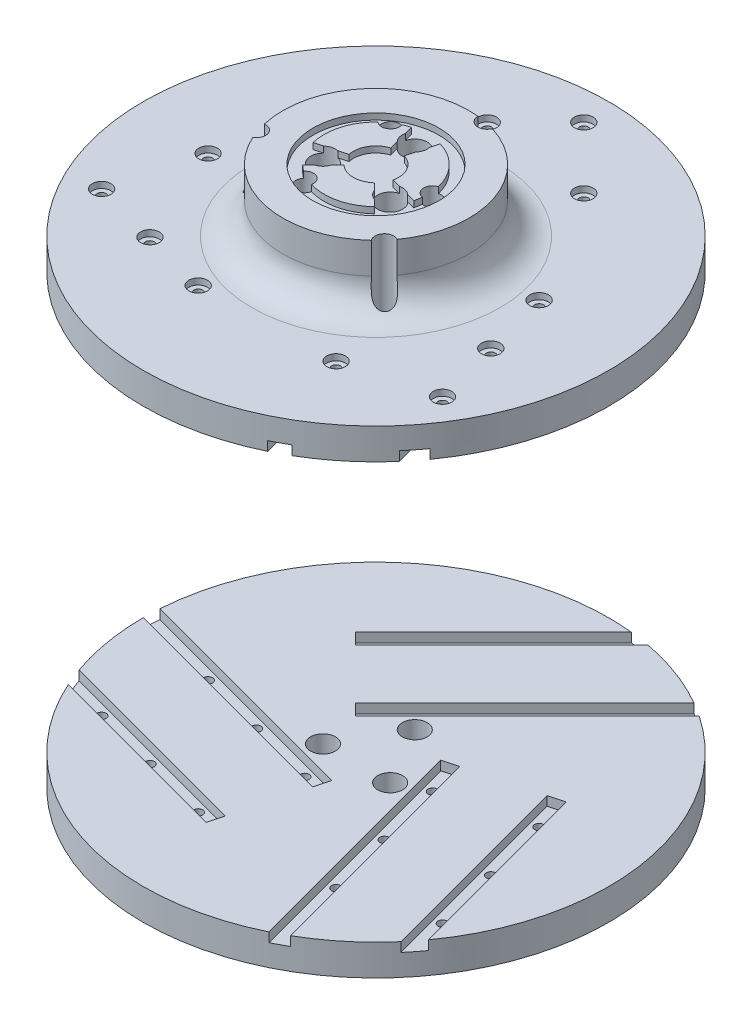
SolidWorks part; units mm, degrees
note: '?' marks a value the reader was unsure of. The reader was unsure of these and kept them because the rebuilt part matched: shared geometry of "草图7<2>", "草图9<2>", "草图14<2>".
ref_plane "前视基准面" through (0, 0, 0) normal (0, 0, 1) x (1, 0, 0)
ref_plane "上视基准面" through (0, 0, 0) normal (0, 1, 0) x (1, 0, 0)
ref_plane "右视基准面" through (0, 0, 0) normal (1, 0, 0) x (0, 0, -1)
sketch "草图1" plane through (0, 0, 0) normal (0, 1, 0) x (1, 0, 0)
  circle A0 centre (0, 0) radius 75
  dimension "D1" = 150
extrude "凸台-拉伸1" add sketch "草图1" along normal blind 10
ref_plane "基准面1" through (0, 144, 0) normal (0, 1, 0) x (1, 0, 0)
sketch "草图2" plane through (0, 144, 0) normal (0, 1, 0) x (1, 0, 0)
  circle A0 centre (0, 0) radius 75
extrude "凸台-拉伸2" add sketch "草图2" along normal blind 10 separate body
sketch "草图3" plane through (0, 154, 0) normal (0, 1, 0) x (1, 0, 0)
  circle A0 centre (0, 0) radius 30
  dimension "D1" = 60
extrude "凸台-拉伸3" add sketch "草图3" along normal blind 20
sketch "草图4" plane through (0, 174, 0) normal (0, 1, 0) x (1, 0, 0)
  line L0 (0, 0) -> (0, 12.5) construction
  line L1 (0, 0) -> (-10.8253, -6.25) construction
  line L2 (0, 0) -> (10.8253, -6.25) construction
  circle A0 centre (0, 0) radius 12.5 construction
  circle A1 centre (0, 12.5) radius 4
  circle A2 centre (-10.8253, -6.25) radius 4
  circle A3 centre (10.8253, -6.25) radius 4
  dimension "D1" = 120
  dimension "D3" = 8
  dimension "D4" = 8
  dimension "D5" = 8
  dimension "D2" = 120
extrude "切除-拉伸1" cut sketch "草图4" against normal through all both and the other way through all
fillet "圆角1" radius 10 1 edges at (0, 154, 30) type face fillet first side face at (0, 174, 30) second side face at (0, 154, 30)
ref_axis "基准轴1" through (-10.8253, 144, 6.25) along (0, 1, 0)?
ref_axis "基准轴2" through (0, 144, -12.5) along (0, 1, 0)?
ref_axis "基准轴3" through (10.8253, 144, 6.25) along (0, 1, 0)?
sketch "草图7" plane through (0, 10, 0) normal (0, 1, 0) x (1, 0, 0)
  line L0 (0, 0) -> (0, 12.5) construction
  line L1 (0, 0) -> (-10.8253, -6.25) construction
  line L2 (0, 0) -> (10.8253, -6.25) construction
  line L3 (0, 12.5) -> (-3.8891, 16.3891) construction
  line L4 (-3.8891, 16.3891) -> (-13.435, 6.8431)
  line L13 (-13.435, 6.8431) -> (-16.9706, 10.3787)
  line L14 (-16.9706, 10.3787) -> (39.598, 66.9472)
  line L15 (39.598, 66.9472) -> (43.1335, 63.4117)
  line L16 (43.1335, 63.4117) -> (-3.8891, 16.3891)
  line L17 (-33.234, 26.6421) -> (16.2635, 76.1396)
  line L18 (16.2635, 76.1396) -> (12.7279, 79.6751)
  line L19 (12.7279, 79.6751) -> (-36.7696, 30.1777)
  line L20 (-36.7696, 30.1777) -> (-33.234, 26.6421)
  line L21 (12.6439, 8.2135) -> (17.4735, 9.5076)
  line L22 (16.1379, -4.8265) -> (12.6439, 8.2135)
  line L23 (17.4735, 9.5076) -> (38.179, -67.7665)
  line L24 (33.3494, -69.0606) -> (16.1379, -4.8265)
  line L25 (38.179, -67.7665) -> (33.3494, -69.0606)
  line L26 (62.6367, -50.8603) -> (44.5194, 16.7545)
  line L27 (39.6898, 15.4604) -> (57.8071, -52.1544)
  line L28 (57.8071, -52.1544) -> (62.6367, -50.8603)
  line L29 (44.5194, 16.7545) -> (39.6898, 15.4604)
  line L30 (0.7912, -15.0566) -> (-0.5029, -19.8863)
  line L31 (-12.2488, -11.5626) -> (0.7912, -15.0566)
  line L32 (-0.5029, -19.8863) -> (-77.777, 0.8192)
  line L33 (-76.4829, 5.6489) -> (-12.2488, -11.5626)
  line L34 (-77.777, 0.8192) -> (-76.4829, 5.6489)
  line L35 (-75.3647, -28.8149) -> (-7.7499, -46.9322)
  line L36 (-6.4558, -42.1026) -> (-74.0706, -23.9852)
  line L37 (-74.0706, -23.9852) -> (-75.3647, -28.8149)
  line L38 (-7.7499, -46.9322) -> (-6.4558, -42.1026)
  line L39 (-15.2028, 8.6109) -> (41.3657, 65.1795) construction
  line L40 (0, 0) -> (-9.5459, 14.2678) construction
  circle A0 centre (0, 0) radius 12.5 construction
  circle A1 centre (0, 12.5) radius 3 construction
  circle A2 centre (-9.5459, 14.2678) radius 1.45
  circle A3 centre (6.0104, 29.8241) radius 1.45
  circle A4 centre (21.5668, 45.3805) radius 1.45
  circle A5 centre (-29.3449, 34.0668) radius 1.45
  circle A6 centre (-13.7886, 49.6231) radius 1.45
  circle A7 centre (1.7678, 65.1795) radius 1.45
  circle A8 centre (44.1751, 8.3801) radius 1.45
  circle A9 centre (49.8692, -12.8703) radius 1.45
  circle A10 centre (55.5632, -34.1207) radius 1.45
  circle A11 centre (28.5173, -41.3676) radius 1.45
  circle A12 centre (22.8232, -20.1172) radius 1.45
  circle A13 centre (17.1292, 1.1331) radius 1.45
  circle A14 centre (-14.8302, -42.4468) radius 1.45
  circle A15 centre (-36.0806, -36.7528) radius 1.45
  circle A16 centre (-57.3309, -31.0588) radius 1.45
  circle A17 centre (-50.084, -4.0129) radius 1.45
  circle A18 centre (-28.8336, -9.7069) radius 1.45
  circle A19 centre (-7.5833, -15.4009) radius 1.45
  point P15 (-15.2028, 8.6109)
  dimension "D1" = 25
  dimension "D4" = 5.5
  dimension "D11" = 2.9
  dimension "D15" = 2.9
  dimension "D16" = 2.9
  dimension "D2" = 120
  dimension "D3" = 120
  dimension "D5" = 13.5
  dimension "D6" = 5
  dimension "D7" = 80
  dimension "D8" = 70
  dimension "D9" = 5
  dimension "D10" = 23
  dimension "D12" = 3
  dimension "D13" = 45
  dimension "D14" = 8
  dimension "D17" = 30
  dimension "D18" = 22
  dimension "D20" = 17.1667
  dimension "D19" = 2
extrude "切除-拉伸5" cut sketch "草图7" against normal blind 3
ref_plane "基准面4" through (0, 77, 0) normal (0, 1, 0) x (1, 0, 0)
sketch "草图9" plane through (0, 144, 0) normal (0, 1, 0) x (1, 0, 0)
  line L0 (0, 0) -> (0, 12.5) construction
  line L1 (0, 0) -> (-10.8253, -6.25) construction
  line L2 (0, 0) -> (10.8253, -6.25) construction
  line L3 (0, 12.5) -> (-3.8891, 16.3891) construction
  line L4 (-3.8891, 16.3891) -> (-13.435, 6.8431)
  line L13 (-13.435, 6.8431) -> (-16.9706, 10.3787)
  line L14 (-16.9706, 10.3787) -> (39.598, 66.9472)
  line L15 (39.598, 66.9472) -> (43.1335, 63.4117)
  line L16 (43.1335, 63.4117) -> (-3.8891, 16.3891)
  line L17 (-33.234, 26.6421) -> (16.2635, 76.1396)
  line L18 (16.2635, 76.1396) -> (12.7279, 79.6751)
  line L19 (12.7279, 79.6751) -> (-36.7696, 30.1777)
  line L20 (-36.7696, 30.1777) -> (-33.234, 26.6421)
  line L21 (12.6439, 8.2135) -> (17.4735, 9.5076)
  line L22 (16.1379, -4.8265) -> (12.6439, 8.2135)
  line L23 (17.4735, 9.5076) -> (38.179, -67.7665)
  line L24 (33.3494, -69.0606) -> (16.1379, -4.8265)
  line L25 (38.179, -67.7665) -> (33.3494, -69.0606)
  line L26 (62.6367, -50.8603) -> (44.5194, 16.7545)
  line L27 (39.6898, 15.4604) -> (57.8071, -52.1544)
  line L28 (57.8071, -52.1544) -> (62.6367, -50.8603)
  line L29 (44.5194, 16.7545) -> (39.6898, 15.4604)
  line L30 (0.7912, -15.0566) -> (-0.5029, -19.8863)
  line L31 (-12.2488, -11.5626) -> (0.7912, -15.0566)
  line L32 (-0.5029, -19.8863) -> (-77.777, 0.8192)
  line L33 (-76.4829, 5.6489) -> (-12.2488, -11.5626)
  line L34 (-77.777, 0.8192) -> (-76.4829, 5.6489)
  line L35 (-75.3647, -28.8149) -> (-7.7499, -46.9322)
  line L36 (-6.4558, -42.1026) -> (-74.0706, -23.9852)
  line L37 (-74.0706, -23.9852) -> (-75.3647, -28.8149)
  line L38 (-7.7499, -46.9322) -> (-6.4558, -42.1026)
  line L39 (41.3657, 65.1795) -> (-15.2028, 8.6109) construction
  line L40 (0, 0) -> (-9.5459, 14.2678) construction
  circle A0 centre (0, 0) radius 12.5 construction
  circle A1 centre (0, 12.5) radius 3 construction
  circle A2 centre (-9.5459, 14.2678) radius 1.45
  circle A3 centre (6.0104, 29.8241) radius 1.45
  circle A4 centre (21.5668, 45.3805) radius 1.45
  circle A5 centre (-29.3449, 34.0668) radius 1.45
  circle A6 centre (-13.7886, 49.6231) radius 1.45
  circle A7 centre (1.7678, 65.1795) radius 1.45
  circle A8 centre (44.1751, 8.3801) radius 1.45
  circle A9 centre (49.8692, -12.8703) radius 1.45
  circle A10 centre (55.5632, -34.1207) radius 1.45
  circle A11 centre (28.5173, -41.3676) radius 1.45
  circle A12 centre (22.8232, -20.1172) radius 1.45
  circle A13 centre (17.1292, 1.1331) radius 1.45
  circle A14 centre (-14.8302, -42.4468) radius 1.45
  circle A15 centre (-36.0806, -36.7528) radius 1.45
  circle A16 centre (-57.3309, -31.0588) radius 1.45
  circle A17 centre (-50.084, -4.0129) radius 1.45
  circle A18 centre (-28.8336, -9.7069) radius 1.45
  circle A19 centre (-7.5833, -15.4009) radius 1.45
  point P15 (-15.2028, 8.6109)
  point P17 (41.3657, 65.1795)
  dimension "D1" = 25
  dimension "D4" = 5.5
  dimension "D11" = 8
  dimension "D2" = 120
  dimension "D3" = 120
  dimension "D5" = 13.5
  dimension "D6" = 5
  dimension "D7" = 80
  dimension "D8" = 70
  dimension "D9" = 5
  dimension "D10" = 23
  dimension "D12" = 3
  dimension "D13" = 45
  dimension "D14" = 30
  dimension "D15" = 22
  dimension "D17" = 17.1667
  dimension "D16" = 2
extrude "切除-拉伸6" cut sketch "草图9" along normal blind 3
extrude "切除-拉伸7" cut sketch "草图7<2>" against normal through all contours A3 | A4 | A2 | A5 | A6 | A7 | A8 | A9 | A10 | A11 | A12 | A13 | A19 | A14 | A15 | A18 | A16 | A17
sketch "草图7<2>" plane through (0, 10, 0) normal (0, 1, 0) x (1, 0, 0) same geometry as "草图7"
sketch "草图13" plane through (0, 0, 0) normal (0, -1, 0) x (1, 0, 0)
  line L0 (0, 0) -> (-7.5833, 15.4009) construction
  circle A0 centre (-14.8302, 42.4468) radius 3
  circle A1 centre (-36.0806, 36.7528) radius 3
  circle A2 centre (-57.3309, 31.0588) radius 3
  circle A4 centre (-7.5833, 15.4009) radius 3
  circle A5 centre (-28.8336, 9.7069) radius 3
  circle A6 centre (-50.084, 4.0129) radius 3
  circle A7 centre (44.1751, -8.3801) radius 3
  circle A8 centre (49.8692, 12.8703) radius 3
  circle A9 centre (55.5632, 34.1207) radius 3
  circle A10 centre (17.1292, -1.1331) radius 3
  circle A11 centre (22.8232, 20.1172) radius 3
  circle A12 centre (28.5173, 41.3676) radius 3
  circle A13 centre (-29.3449, -34.0668) radius 3
  circle A14 centre (-13.7886, -49.6231) radius 3
  circle A15 centre (1.7678, -65.1795) radius 3
  circle A16 centre (-9.5459, -14.2678) radius 3
  circle A17 centre (6.0104, -29.8241) radius 3
  circle A18 centre (21.5668, -45.3805) radius 3
  dimension "D1" = 17.1667
extrude "切除-拉伸8" cut sketch "草图13" against normal blind 2
extrude "切除-拉伸9" cut sketch "草图9<2>" along normal through all contours A7 | A6 | A5 | A4 | A3 | A2 | A13 | A8 | A9 | A10 | A12 | A11 | A14 | A15 | A16 | A17 | A18 | A19
sketch "草图9<2>" plane through (0, 144, 0) normal (0, 1, 0) x (1, 0, 0) same geometry as "草图9"
sketch "草图14" plane through (0, 154, 0) normal (0, 1, 0) x (1, 0, 0)
  line L0 (0, 0) -> (-9.5459, 14.2678) construction
  circle A0 centre (-9.5459, 14.2678) radius 2.8694
  circle A1 centre (6.0104, 29.8241) radius 3
  circle A2 centre (21.5668, 45.3805) radius 3
  circle A3 centre (-29.3449, 34.0668) radius 3
  circle A4 centre (-13.7886, 49.6231) radius 3
  circle A5 centre (1.7678, 65.1795) radius 3
  circle A6 centre (17.1292, 1.1331) radius 2.8694
  circle A7 centre (22.8232, -20.1172) radius 3
  circle A8 centre (28.5173, -41.3676) radius 3
  circle A9 centre (44.1751, 8.3801) radius 3
  circle A10 centre (49.8692, -12.8703) radius 3
  circle A11 centre (55.5632, -34.1207) radius 3
  circle A12 centre (-7.5833, -15.4009) radius 2.8694
  circle A13 centre (-28.8336, -9.7069) radius 3
  circle A14 centre (-50.084, -4.0129) radius 3
  circle A15 centre (-14.8302, -42.4468) radius 3
  circle A16 centre (-36.0806, -36.7528) radius 3
  circle A17 centre (-57.3309, -31.0588) radius 3
  dimension "D1" = 17.1667
extrude "切除-拉伸10" cut sketch "草图14" against normal blind 2
extrude "切除-拉伸11" cut sketch "草图14<2>" along normal through all
sketch "草图14<2>" plane through (0, 154, 0) normal (0, 1, 0) x (1, 0, 0) same geometry as "草图14"
sketch "草图15" plane through (0, 77, 0) normal (0, 1, 0) x (1, 0, 0)
  line L0 (-100, 100) -> (100, -100) construction
  line L1 (-100, 100) -> (100, 100)
  line L2 (-100, 100) -> (-100, -100)
  line L3 (-100, -100) -> (100, -100)
  line L4 (100, 100) -> (100, -100)
  line L5 (100, 100) -> (-100, -100) construction
  point P5 (0, 0)
  dimension "D1" = 200
  dimension "D2" = 200
sketch "草图16" plane through (0, 174, 0) normal (0, 1, 0) x (1, 0, 0)
  line L0 (0, 7) -> (0, 17) construction
  line L13 (-1.8117, 6.7615) -> (-4.3999, 16.4207) construction
  line L14 (1.8117, 6.7615) -> (4.3999, 16.4207) construction
  line L15 (6.7615, -1.8117) -> (16.4207, -4.3999) construction
  line L16 (4.9497, -4.9497) -> (12.0208, -12.0208) construction
  line L17 (-4.9497, -4.9497) -> (-12.0208, -12.0208) construction
  line L18 (-6.7615, -1.8117) -> (-16.4207, -4.3999) construction
  line L19 (-7.1229, -1.598) -> (-16.206, -4.0318)
  line L20 (-2.1776, 6.9677) -> (-4.6114, 16.0507)
  line L21 (7.1229, -1.598) -> (16.206, -4.0318)
  line L22 (2.1776, 6.9677) -> (4.6114, 16.0507)
  line L23 (-4.9454, -5.3697) -> (-11.5946, -12.0189)
  line L24 (4.9454, -5.3697) -> (11.5946, -12.0189)
  arc A9 (-1.8117, 6.7615) -> (-6.7615, -1.8117) centre (0, 0) ccw construction
  arc A17 (-4.3999, 16.4207) -> (-16.4207, -4.3999) centre (0, 0) ccw construction
  circle A18 centre (0, 0) radius 20 construction
  arc A19 (-4.9497, -4.9497) -> (4.9497, -4.9497) centre (0, 0) ccw construction
  arc A20 (6.7615, -1.8117) -> (1.8117, 6.7615) centre (0, 0) ccw construction
  arc A21 (16.4207, -4.3999) -> (4.3999, 16.4207) centre (0, 0) ccw construction
  arc A22 (-12.0208, -12.0208) -> (12.0208, -12.0208) centre (0, 0) ccw construction
  arc A23 (-4.6114, 16.0507) -> (-16.206, -4.0318) centre (0, 0) ccw
  arc A24 (-2.1776, 6.9677) -> (-7.1229, -1.598) centre (0, 0) ccw
  arc A25 (16.206, -4.0318) -> (4.6114, 16.0507) centre (0, 0) ccw
  arc A26 (7.1229, -1.598) -> (2.1776, 6.9677) centre (0, 0) ccw
  arc A27 (-11.5946, -12.0189) -> (11.5946, -12.0189) centre (0, 0) ccw
  arc A28 (-4.9454, -5.3697) -> (4.9454, -5.3697) centre (0, 0) ccw
  circle A29 centre (0, 0) radius 20.3
  point P13 (0, 0)
  point P35 (0, 0)
  dimension "D1" = 14
  dimension "D2" = 34
  dimension "D4" = 15
  dimension "D5" = 15
  dimension "D6" = 3
  dimension "D3" = 40
  dimension "D8" = 0.3
  dimension "D7" = 0.3
extrude "切除-拉伸12" cut sketch "草图16" against normal blind 2
sketch "草图18" plane through (0, 144, 0) normal (0, -1, 0) x (1, 0, 0)
  line L0 (-7.7499, 46.9322) -> (-6.4558, 42.1026) construction
  line L1 (-6.4558, 42.1026) -> (-70.7552, 24.8736) construction
  line L2 (-7.7499, 46.9322) -> (-68.4425, 30.6697) construction
  line L3 (-0.5029, 19.8863) -> (-75, -0.0751) construction
  line L4 (-0.5029, 19.8863) -> (0.7912, 15.0566) construction
  line L5 (0.7912, 15.0566) -> (-74.8193, -5.2031) construction
  line L6 (-68.4425, 30.6697) -> (-72.0493, 29.7032) construction
  line L7 (-72.0493, 29.7032) -> (-70.7552, 24.8736) construction
  line L8 (-75, -0.0751) -> (-76.1134, -0.3735) construction
  line L9 (-76.1134, -0.3735) -> (-74.8193, -5.2031) construction
  line L10 (-7.5377, 47.2996) -> (-68.5201, 30.9594)
  line L11 (-68.5201, 30.9594) -> (-72.4168, 29.9153)
  line L12 (-72.4168, 29.9153) -> (-70.9674, 24.5062)
  line L13 (-6.0883, 41.8904) -> (-70.9674, 24.5062)
  line L14 (-7.5377, 47.2996) -> (-6.0883, 41.8904)
  line L15 (-0.2908, 20.2537) -> (-75.0776, 0.2146)
  line L16 (-75.0776, 0.2146) -> (-76.4808, -0.1614)
  line L17 (-76.4808, -0.1614) -> (-75.0314, -5.5705)
  line L18 (1.1586, 14.8445) -> (-75.0314, -5.5705)
  line L19 (-0.2908, 20.2537) -> (1.1586, 14.8445)
  line L20 (44.7315, -17.122) -> (61.0717, 43.8604)
  line L21 (61.0717, 43.8604) -> (62.1158, 47.7571)
  line L22 (62.1158, 47.7571) -> (56.7066, 49.2065)
  line L23 (39.3224, -15.6726) -> (56.7066, 49.2065)
  line L24 (44.7315, -17.122) -> (39.3224, -15.6726)
  line L25 (17.6856, -9.875) -> (37.7247, 64.9118)
  line L26 (37.7247, 64.9118) -> (38.1007, 66.315)
  line L27 (38.1007, 66.315) -> (32.6915, 67.7644)
  line L28 (12.2764, -8.4256) -> (32.6915, 67.7644)
  line L29 (17.6856, -9.875) -> (12.2764, -8.4256)
  line L30 (44.5194, -16.7545) -> (39.6898, -15.4604) construction
  line L31 (39.6898, -15.4604) -> (56.9188, 48.8391) construction
  line L32 (44.5194, -16.7545) -> (60.7819, 43.9381) construction
  line L33 (17.4735, -9.5076) -> (37.4349, 64.9894) construction
  line L34 (17.4735, -9.5076) -> (12.6439, -8.2135) construction
  line L35 (12.6439, -8.2135) -> (32.9036, 67.397) construction
  line L36 (60.7819, 43.9381) -> (61.7484, 47.545) construction
  line L37 (61.7484, 47.545) -> (56.9188, 48.8391) construction
  line L38 (37.4349, 64.9894) -> (37.7332, 66.1029) construction
  line L39 (37.7332, 66.1029) -> (32.9036, 67.397) construction
  line L40 (-37.1938, -30.1777) -> (7.4484, -74.8199)
  line L41 (7.4484, -74.8199) -> (10.3009, -77.6724)
  line L42 (10.3009, -77.6724) -> (14.2607, -73.7126)
  line L43 (-33.234, -26.2179) -> (14.2607, -73.7126)
  line L44 (-37.1938, -30.1777) -> (-33.234, -26.2179)
  line L45 (-17.3948, -10.3787) -> (37.3529, -65.1264)
  line L46 (37.3529, -65.1264) -> (38.3801, -66.1537)
  line L47 (38.3801, -66.1537) -> (42.3399, -62.1939)
  line L48 (-13.435, -6.4189) -> (42.3399, -62.1939)
  line L49 (-17.3948, -10.3787) -> (-13.435, -6.4189)
  line L50 (-36.7696, -30.1777) -> (-33.234, -26.6421) construction
  line L51 (-33.234, -26.6421) -> (13.8365, -73.7126) construction
  line L52 (-36.7696, -30.1777) -> (7.6605, -74.6077) construction
  line L53 (-16.9706, -10.3787) -> (37.5651, -64.9143) construction
  line L54 (-16.9706, -10.3787) -> (-13.435, -6.8431) construction
  line L55 (-13.435, -6.8431) -> (41.9157, -62.1939) construction
  line L56 (7.6605, -74.6077) -> (10.3009, -77.2482) construction
  line L57 (10.3009, -77.2482) -> (13.8365, -73.7126) construction
  line L58 (37.5651, -64.9143) -> (38.3801, -65.7294) construction
  line L59 (38.3801, -65.7294) -> (41.9157, -62.1939) construction
  point P70 (0, 0)
  dimension "D1" = 90
  dimension "D2" = 90
  dimension "D3" = 90
  dimension "D4" = 90
  dimension "D5" = 0.3
extrude "切除-拉伸14" cut sketch "草图18" against normal up to surface (3 mm away) up to face at (-36.0806, 147, 38.2028)
